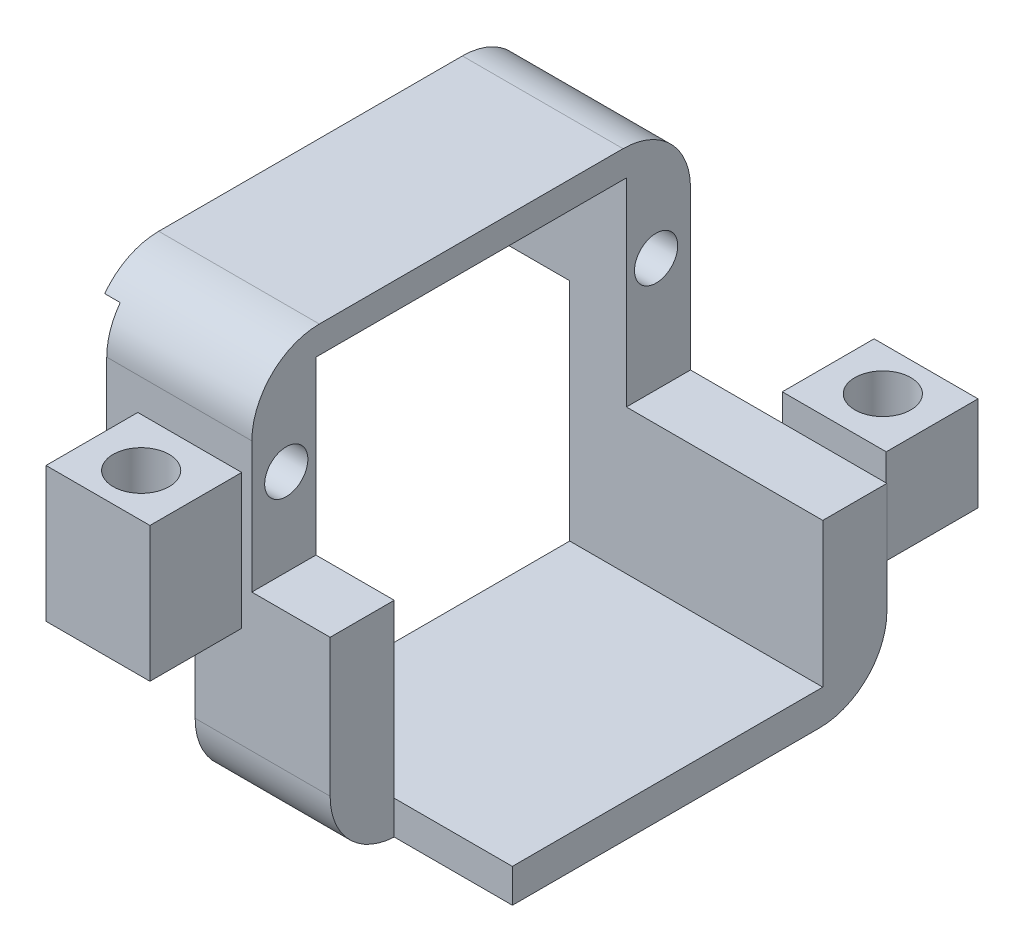
SolidWorks part; units mm, degrees
ref_plane "Front Plane" through (0, 0, 0) normal (0, 0, 1) x (1, 0, 0)
ref_plane "Top Plane" through (0, 0, 0) normal (0, 1, 0) x (1, 0, 0)
ref_plane "Right Plane" through (0, 0, 0) normal (1, 0, 0) x (0, 0, -1)
sketch "Sketch1" plane through (0, 0, 0) normal (0, 1, 0) x (1, 0, 0)
  line L0 (-1.1, 16.25) -> (-1.1, 11.5)
  line L1 (-17.65, -16.25) -> (17.65, -16.25)
  line L2 (-17.65, -16.25) -> (-17.65, 16.25)
  line L3 (-17.65, 16.25) -> (17.65, 16.25)
  line L4 (17.65, -16.25) -> (17.65, 16.25)
  line L5 (-17.65, -16.25) -> (17.65, 16.25) construction
  line L6 (-17.65, 16.25) -> (17.65, -16.25) construction
  line L7 (-1.1, 11.5) -> (17.65, 11.5)
  line L8 (-1.1, -16.25) -> (-1.1, -11.5)
  line L9 (-1.1, -11.5) -> (17.65, -11.5)
  line L10 (-1.1, 11.5) -> (-1.1, -11.5) construction
  line L11 (8.9, -11.5) -> (8.9, -16.25)
  line L12 (-8.8, 16.25) -> (-8.8, 11.5)
  line L13 (-8.8, 11.5) -> (-3.8, 11.5)
  line L14 (-3.8, 11.5) -> (-3.8, 16.25)
  line L15 (-3.8, -16.25) -> (-3.8, -11.5)
  line L16 (-3.8, -11.5) -> (-8.8, -11.5)
  line L17 (-8.8, -11.5) -> (-8.8, -16.25)
  line L18 (-8.8, 11.5) -> (-8.8, -11.5)
  line L19 (17.6, 16.25) -> (17.6, 23.05)
  line L20 (17.6, 23.05) -> (9.9, 23.05)
  line L21 (9.9, 23.05) -> (9.9, 16.25)
  line L22 (-5.35, -16.25) -> (-5.35, -23.05)
  line L23 (-5.35, -23.05) -> (2.35, -23.05)
  line L24 (2.35, -23.05) -> (2.35, -16.25)
  line L28 (-1.1, 11.5) -> (-1.1, -11.5)
  circle A0 centre (13.75, 19.85) radius 2.075
  circle A2 centre (-1.5, -19.85) radius 2.075
  point P0 (0, 0)
  point P11 (-1.1, 0)
  point P31 (13.75, 23.05)
  point P45 (-1.5, -23.05)
  dimension "D11" = 4.15
  dimension "D19" = 4.15
  dimension "D1" = 32.5
  dimension "D2" = 23
  dimension "D3" = 8.75
  dimension "D4" = 10
  dimension "D5" = 16.55
  dimension "D6" = 2.7
  dimension "D7" = 5
  dimension "D8" = 13.75
  dimension "D9" = 7.7
  dimension "D10" = 6.8
  dimension "D12" = 1.5
  dimension "D13" = 19.85
  dimension "D16" = 7.7
  dimension "D17" = 6.8
  dimension "D20" = 19.85
extrude "Boss-Extrude1" add sketch "Sketch1" against normal blind 2.5 contours L7 L28 L9 L4 | L0 L7 L4 L3 | L11 L9 L8 L1 region at (8.275, 0, -13.875) region at (8.275, 0, 0) region at (3.9, 0, 13.875)
extrude "Boss-Extrude2" add sketch "Sketch1<3>" along normal blind 12.7 contours L0 L7 L4 L3 | L11 L9 L8 L1 region at (8.275, 0, -13.875) region at (3.9, 0, 13.875)
sketch "Sketch1<3>" plane through (0, 0, 0) normal (0, 1, 0) x (1, 0, 0) same geometry as "Sketch1"
sketch "Sketch3" plane through (0, 0, 0) normal (0, 1, 0) x (1, 0, 0)
  line L0 (3.1, 16.25) -> (3.1, 11.5)
  line L1 (-17.65, 16.25) -> (17.65, 16.25) construction
  line L2 (-1.1, 11.5) -> (17.65, 11.5) construction
  line L3 (3.1, 11.5) -> (-17.65, 11.5)
  line L4 (-17.65, -16.25) -> (-17.65, 16.25) construction
  line L5 (3.1, -16.25) -> (3.1, -11.5)
  line L6 (-17.65, -16.25) -> (17.65, -16.25) construction
  line L7 (-1.1, -11.5) -> (17.65, -11.5) construction
  line L8 (3.1, -11.5) -> (-17.65, -11.5)
  line L9 (3.1, 11.5) -> (3.1, -11.5)
  line L10 (-7.65, -11.5) -> (-7.65, -16.275)
  line L11 (3.1, 16.25) -> (-17.65, 16.25)
  line L12 (-17.65, 16.25) -> (-17.65, 11.5)
  line L13 (-17.65, -11.5) -> (-17.65, -16.25)
  line L14 (-17.65, -16.25) -> (3.1, -16.25)
  line L15 (-8.8, 11.5) -> (-8.8, -11.5)
  line L16 (-8.8, 11.5) -> (-8.8, 16.25)
  line L17 (-8.8, -11.5) -> (-8.8, -16.25)
  dimension "D1" = 20.75
  dimension "D2" = 10
extrude "Boss-Extrude3" add sketch "Sketch3" along normal blind 12.7 from surface contours L11 L12 L3 L0 | L10 L14 L5 L8 region at (-2.85, 0, -13.875) region at (-2.275, 0, 13.875) starting at face at (8.275, 12.7, -13.875)
extrude "Boss-Extrude4" add sketch "Sketch3<3>" along normal blind 2 from surface contours L16 L3 L0 L11 | L3 L15 L8 L9 | L10 L14 L5 L8 | L8 L17 L14 L10 region at (-2.85, 0, -13.875) region at (-2.85, 0, 0) region at (-2.275, 0, 13.875) region at (-8.225, 0, 13.875) starting at face at (-2.275, 25.4, 13.875)
sketch "Sketch3<3>" plane through (0, 0, 0) normal (0, 1, 0) x (1, 0, 0) same geometry as "Sketch3"
sketch "Sketch2" plane through (0, 0, 0) normal (1, 0, 0) x (0, 0, -1)
  line L0 (13.7, 6.45) -> (-13.7, 6.45) construction
  line L1 (-13.7, 19.15) -> (13.7, 19.15) construction
  circle A0 centre (13.7, 6.45) radius 1.6
  circle A1 centre (-13.7, 6.45) radius 1.6
  circle A2 centre (-13.7, 19.15) radius 1.6
  circle A3 centre (13.7, 19.15) radius 1.6
  point P4 (0, 6.45)
  dimension "D1" = 3.2
  dimension "D2" = 3.2
  dimension "D6" = 3.2
  dimension "D7" = 3.2
  dimension "D3" = 27.4
  dimension "D4" = 6.45
  dimension "D5" = 6.45
extrude "Cut-Extrude1" cut sketch "Sketch2" along normal blind 8 from surface contours A1 | A0 region at (0, 6.45, -13.7) region at (0, 6.45, 13.7) starting at face at (-1.1, 5.725, 0)
extrude "Cut-Extrude2" cut sketch "Sketch2<3>" against normal blind 8 from surface contours A3 | A2 region at (0, 19.15, 13.7) region at (0, 19.15, -13.7) starting at face at (3.1, 19.55, 0)
sketch "Sketch2<3>" plane through (0, 0, 0) normal (1, 0, 0) x (0, 0, -1) same geometry as "Sketch2"
extrude "Boss-Extrude5" add sketch "Sketch1<4>" along normal blind 10 from offset 10 contours L23 L24 L1 L22 A2 region at (0.625, 0, 16.3527)
sketch "Sketch1<4>" plane through (0, 0, 0) normal (0, 1, 0) x (1, 0, 0) same geometry as "Sketch1"
extrude "Boss-Extrude6" add sketch "Sketch1<7>" against normal blind 7 from surface contours L20 L21 L3 L19 A0 region at (10.0027, 0, -19.65) starting at face at (10.375, 12.7, -13.875)
sketch "Sketch1<7>" plane through (0, 0, 0) normal (0, 1, 0) x (1, 0, 0) same geometry as "Sketch1"
fillet "Fillet1" radius 5 4 edges at (3.9, -2.5, 16.25) (-2.85, 27.4, 16.25) (8.275, -2.5, -16.25) (-2.85, 27.4, -16.25)
sketch "Sketch5" plane through (0, 0, 0) normal (0, 1, 0) x (1, 0, 0)
  line L1 (17.65, 16.25) -> (3.1, 16.25)
  line L2 (17.65, 16.25) -> (17.65, 11.5)
  line L3 (17.65, 11.5) -> (3.1, 11.5)
  line L4 (3.1, 16.25) -> (3.1, 11.5)
extrude "Cut-Extrude3" cut sketch "Sketch5" against normal blind 2 from surface starting at face at (12.0625, 12.7, -16.7625)
sketch "Sketch6" plane through (0, 0, 0) normal (0, 1, 0) x (1, 0, 0)
  line L1 (-8.8, 11.5) -> (-1.1, 11.5)
  line L2 (-8.8, 11.5) -> (-8.8, 16.25)
  line L3 (-8.8, 16.25) -> (-1.1, 16.25)
  line L4 (-1.1, 11.5) -> (-1.1, 16.25)
extrude "Cut-Extrude4" cut sketch "Sketch6" along normal blind 4 from surface starting at face at (-4.95, 12.7, -13.875)
